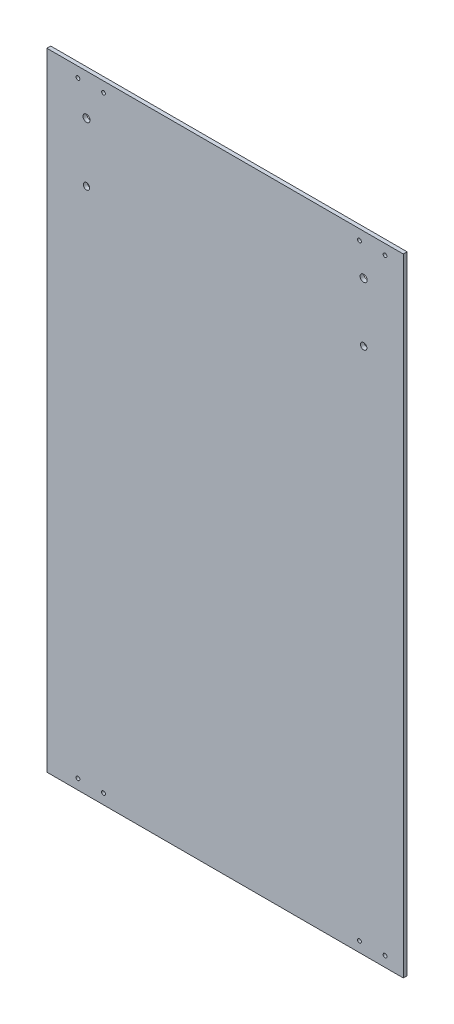
SolidWorks part; units mm, degrees
ref_plane "前视基准面" through (0, 0, 0) normal (0, 0, 1) x (1, 0, 0)
ref_plane "上视基准面" through (0, 0, 0) normal (0, 1, 0) x (1, 0, 0)
ref_plane "右视基准面" through (0, 0, 0) normal (1, 0, 0) x (0, 0, -1)
other "Configuration Table"
sketch "草图1" plane through (0, 0, 0) normal (0, 0, 1) x (1, 0, 0)
  line L0 (-99.3737, -240) -> (-123.3737, -240) construction
  line L1 (-139.28, 245) -> (139.28, 245)
  line L2 (-139.28, 245) -> (-139.28, -245)
  line L3 (-139.28, -245) -> (139.28, -245)
  line L4 (139.28, 245) -> (139.28, -245)
  line L5 (-139.28, 245) -> (139.28, -245) construction
  line L6 (-139.28, -245) -> (139.28, 245) construction
  line L7 (-52.7223, -240) -> (-100.7223, -240) construction
  line L8 (123.371, -240) -> (99.371, -240) construction
  line L9 (245.0535, 242) -> (105.7722, 242) construction
  line L10 (117.8124, -240) -> (128.3124, -240) construction
  line L11 (-123.3737, 242) -> (-99.3737, 242) construction
  line L12 (-100.7223, 242) -> (-52.7223, 242) construction
  line L13 (88.4517, 242) -> (105.7722, 242) construction
  circle A0 centre (104.9991, 237) radius 1.5
  circle A1 centre (124.9991, 237) radius 1.5
  circle A2 centre (-95.0009, 237) radius 1.5
  circle A3 centre (-115.0009, 237) radius 1.5
  circle A4 centre (124.9991, -237) radius 1.5
  circle A5 centre (104.9991, -237) radius 1.5
  circle A6 centre (-95.0009, -237) radius 1.5
  circle A7 centre (-115.0009, -237) radius 1.5
  point P0 (0, 0)
  dimension "D3" = 24.2791
  dimension "D4" = 20
  dimension "D6" = 3
  dimension "D9" = 14.2809
  dimension "D1" = 490
  dimension "D2" = 278.56
  dimension "D5" = 3
  dimension "D7" = 3
  dimension "D8" = 20
  dimension "D10" = 3
  dimension "D11" = 24.2791
  dimension "D12" = 5
  dimension "D13" = 5
  dimension "D14" = 20
  dimension "D15" = 20
  dimension "D16" = 14.2809
  dimension "D17" = 5
  dimension "D18" = 5
extrude "凸台-拉伸1" add sketch "草图1" along normal blind 3
sketch "草图2" plane through (0, 0, 0) normal (0, 0, -1) x (-1, 0, 0)
  circle A0 centre (-108.2755, 167.0881) radius 2.5
  circle A1 centre (108.2845, 167.0881) radius 2.5
  dimension "D1" = 5
  dimension "D2" = 5
extrude "切除-拉伸1" cut sketch "草图2" against normal blind 10
sketch "草图3" plane through (0, 0, 0) normal (0, 0, -1) x (-1, 0, 0)
  circle A0 centre (108.2845, 213.0881) radius 2.75 construction
  circle A1 centre (108.2845, 213.0881) radius 2.75
  circle A2 centre (-108.2755, 213.0881) radius 2.75 construction
  circle A3 centre (-108.2755, 213.0881) radius 2.75
extrude "切除-拉伸2" cut sketch "草图3" against normal through all both and the other way through all
